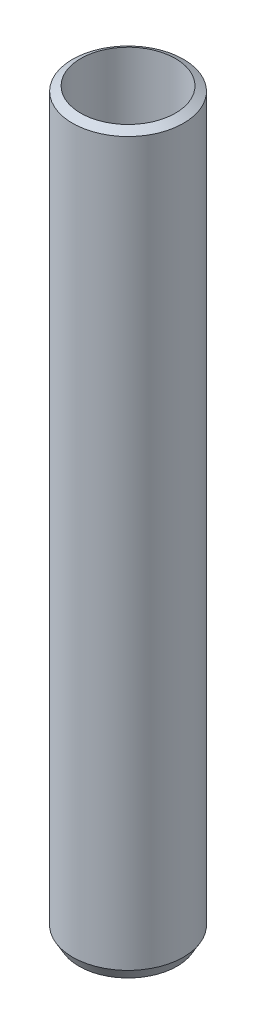
SolidWorks part; units mm, degrees
ref_plane "Front Plane" through (0, 0, 0) normal (0, 0, 1) x (1, 0, 0)
ref_plane "Top Plane" through (0, 0, 0) normal (0, 1, 0) x (1, 0, 0)
ref_plane "Right Plane" through (0, 0, 0) normal (1, 0, 0) x (0, 0, -1)
sketch "Sketch1" plane through (0, 0, 0) normal (0, 1, 0) x (1, 0, 0)
  circle A0 centre (0, 0) radius 45
  dimension "SHAFT_OD" = 90
extrude "Boss-Extrude1" add sketch "Sketch1" along normal blind 600
sketch "Sketch2" plane through (0, 0, 0) normal (0, 1, 0) x (1, 0, 0)
  circle A0 centre (0, 0) radius 38.4233
  dimension "BORE_D" = 76.8466
extrude "Cut-Extrude1" cut sketch "Sketch2" along normal through all
chamfer "Chamfer1" distance 5.2197 angle 60 2 edges at (0, 600, 45) (0, 0, 45) first distance on face at (0, 600, 45) first distance on face at (0, 0, 38.4233)
